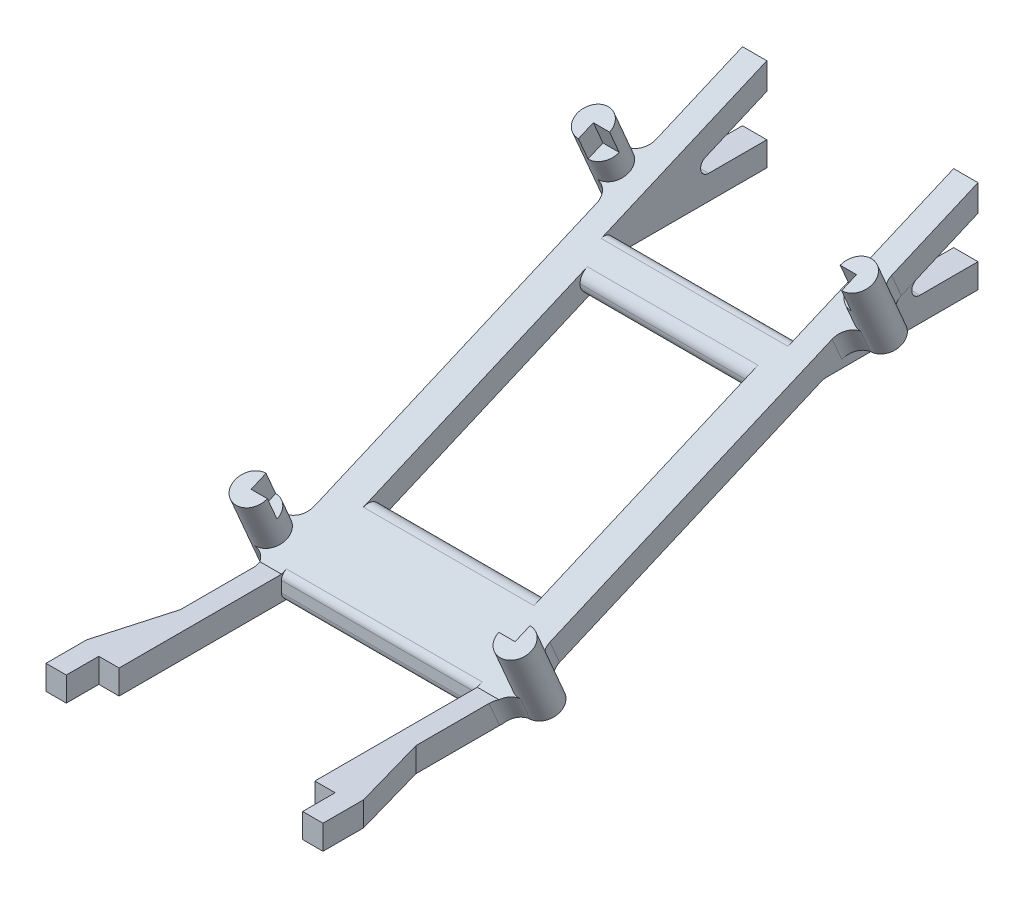
SolidWorks part; units mm, degrees
ref_plane "Front Plane" through (0, 0, 0) normal (0, 0, 1) x (1, 0, 0)
ref_plane "Top Plane" through (0, 0, 0) normal (0, 1, 0) x (1, 0, 0)
ref_plane "Right Plane" through (0, 0, 0) normal (1, 0, 0) x (0, 0, -1)
sketch "Sketch1" plane through (0, 0, 0) normal (1, 0, 0) x (0, 0, -1)
  line L0 (0, 0) -> (0, 30.9996) construction
  line L1 (64.2, 35.525) -> (64.2, -15.505) construction
  line L2 (0, 0) -> (20.617, 0)
  line L3 (20.617, 0) -> (60.2, 17)
  line L4 (60.2, 17) -> (79.2, 17)
  line L5 (79.2, 17) -> (79.2, 20)
  line L6 (79.2, 20) -> (67.1852, 20)
  line L7 (67.1852, 20) -> (79.2, 25.1601)
  line L8 (79.2, 25.1601) -> (79.2, 28.425)
  line L9 (79.2, 28.425) -> (20, 3)
  line L10 (20, 3) -> (0, 3)
  line L11 (0, 3) -> (0, 0)
  dimension "D1" = 64.2
  dimension "D2" = 3
  dimension "D3" = 3
  dimension "D4" = 20
  dimension "D5" = 4
  dimension "D6" = 17
  dimension "D7" = 3
  dimension "D8" = 15
extrude "Boss-Extrude1" add sketch "Sketch1" along normal blind 29
sketch "Sketch2" plane through (0, 3, 0) normal (0, 1, 0) x (1, 0, 0)
  line L0 (29, 0) -> (0, 0) construction
  line L1 (2.45, -20) -> (26.55, -20)
  line L2 (2.45, -20) -> (2.45, 20)
  line L3 (2.45, 20) -> (26.55, 20)
  line L4 (26.55, -20) -> (26.55, 20)
  line L5 (2.45, -20) -> (26.55, 20) construction
  line L6 (2.45, 20) -> (26.55, -20) construction
  line L7 (29, 20) -> (0, 20) construction
  point P0 (14.5, 0)
  dimension "D1" = 24.1
extrude "Cut-Extrude1" cut sketch "Sketch2" against normal blind 28
sketch "Sketch3" plane through (0, 0, 0) normal (0, -1, 0) x (1, 0, 0)
  line L0 (14.5, -60.2) -> (14.5, -10.4345) construction
  line L1 (29, -60.2) -> (0, -60.2) construction
  line L2 (0, -20.617) -> (0, -60.2) construction
  line L3 (4, -55.2) -> (25, -55.2)
  line L4 (4, -55.2) -> (4, -30.617)
  line L5 (4, -30.617) -> (25, -30.617)
  line L6 (25, -55.2) -> (25, -30.617)
  line L7 (4, -55.2) -> (25, -30.617) construction
  line L8 (4, -30.617) -> (25, -55.2) construction
  line L9 (29, -20.617) -> (0, -20.617) construction
  point P4 (14.5, -42.9085)
  dimension "D1" = 4
  dimension "D2" = 10
  dimension "D3" = 5
extrude "Cut-Extrude2" cut sketch "Sketch3" against normal blind 28
sketch "Sketch4" plane through (0, 17, 0) normal (0, -1, 0) x (1, 0, 0)
  line L0 (29, -79.2) -> (0, -79.2) construction
  line L1 (3, -98.2) -> (26, -98.2)
  line L2 (3, -98.2) -> (3, -60.2)
  line L3 (3, -60.2) -> (26, -60.2)
  line L4 (26, -98.2) -> (26, -60.2)
  line L5 (3, -98.2) -> (26, -60.2) construction
  line L6 (3, -60.2) -> (26, -98.2) construction
  line L7 (29, -60.2) -> (0, -60.2) construction
  point P0 (14.5, -79.2)
  point P7 (25.5, -60.2)
  dimension "D1" = 23
extrude "Cut-Extrude3" cut sketch "Sketch4" against normal through all
sketch "Sketch5" plane through (0, 0, 0) normal (0, 1, 0) x (1, 0, 0)
  line L0 (-16.6049, 23) -> (48.1653, 23) construction
  dimension "D1" = 23
sketch "Sketch6" plane through (0, -4.7191, -2.0267) normal (0, 0.9188, 0.3946) x (1, 0, 0)
  line L1 (-16.6049, 21.1334) -> (48.1653, 21.1334) construction
  line L2 (-16.6049, 21.1334) -> (48.1653, 21.1334) construction
  line L3 (48.1653, 22.6334) -> (-16.6049, 22.6334) construction
  line L4 (-1.75, 24.6334) -> (-1.75, 22.6334)
  line L5 (-1.75, 22.6334) -> (0.25, 22.6334)
  line L6 (30.75, 24.6334) -> (30.75, 22.6334)
  line L7 (30.75, 22.6334) -> (28.75, 22.6334)
  line L8 (-1.75, 22.6334) -> (14.5, 31.1154) construction
  line L9 (25, 31.1154) -> (4, 31.1154) construction
  line L10 (14.5, 31.1154) -> (30.75, 22.6334) construction
  circle A0 centre (-1.75, 22.6334) radius 2
  circle A1 centre (30.75, 22.6334) radius 2
  line M14 (0, 83.9896) -> (0, 19.5607)
  line M18 (29, 19.5607) -> (29, 83.9896)
  dimension "D2" = 4
  dimension "D1" = 1.5
  dimension "D3" = 32.5
extrude "Boss-Extrude2" add sketch "Sketch6" along normal blind 6 separate body contours L7 A1 L6 | L4 A0 L5 | A0 L5 M14 | L7 A1 M18
sketch "Sketch7" plane through (0, -4.7191, -2.0267) normal (0, -0.9188, -0.3946) x (1, 0, 0)
  arc A0 (30.75, -24.6334) -> (28.75, -22.6334) centre (30.75, -22.6334) ccw construction
  circle A1 centre (30.75, -22.6334) radius 2
  arc A2 (0.25, -22.6334) -> (-1.75, -24.6334) centre (-1.75, -22.6334) ccw construction
  circle A3 centre (-1.75, -22.6334) radius 2
  point P3 (28.25, -22.9332)
  point P8 (-0.25, -22.9709)
extrude "Boss-Extrude3" add sketch "Sketch7" against normal blind 3
sketch "Sketch8" plane through (0, -4.7191, -2.0267) normal (0, -0.9188, -0.3946) x (1, 0, 0)
  line L0 (-1.75, -20.6334) -> (30.75, -20.6334)
  line L1 (-1.75, -24.6334) -> (30.75, -24.6334)
  circle A0 centre (-1.75, -22.6334) radius 2 construction
  circle A1 centre (-1.75, -22.6334) radius 2
  circle A2 centre (30.75, -22.6334) radius 2 construction
  circle A3 centre (30.75, -22.6334) radius 2
  circle M2 centre (30.75, -22.6334) radius 2
extrude "Boss-Extrude4" add sketch "Sketch8" along normal blind 3 contours A1 L1 L0 M2 | M2 | A1
fillet "Fillet5" radius 1 1 edges at (14.5, 17, -60.2)
fillet "Fillet1" radius 2 6 edges at (1.5, 17, -60.2) (27.5, 17, -60.2) (29, 2.045, -21.5775) (29, 3.6235, -25.2529) (0, 3.6235, -25.2529) (0, 2.045, -21.5775)
sketch "Sketch9" plane through (0, -4.7191, -2.0267) normal (0, 0.9188, 0.3946) x (1, 0, 0)
  line L0 (-1.7, 66.4334) -> (-1.7, 68.4334)
  line L1 (-1.7, 68.4334) -> (0.3, 68.4334)
  line L2 (28.7, 68.4334) -> (30.7, 68.4334)
  line L3 (30.7, 68.4334) -> (30.7, 66.4334)
  line L4 (-1.7, 68.4334) -> (14.5, 57.8698) construction
  line L5 (4, 57.8698) -> (25, 57.8698) construction
  line L6 (14.5, 57.8698) -> (30.7, 68.4334) construction
  line L7 (-1.75, 22.6334) -> (0.25, 22.6334) construction
  line L8 (0.25, 22.6334) -> (28.75, 22.6334) construction
  line L9 (0.3, 68.4334) -> (28.7, 68.4334) construction
  circle A0 centre (-1.7, 68.4334) radius 2
  circle A1 centre (30.7, 68.4334) radius 2
  arc A2 (-1.875, 20.6373) -> (-1.875, 24.6295) centre (-1.75, 22.6334) ccw construction
  arc A3 (30.875, 24.6295) -> (30.875, 20.6373) centre (30.75, 22.6334) ccw construction
  arc A4 (0.25, 22.6334) -> (-1.75, 24.6334) centre (-1.75, 22.6334) ccw construction
  point P20 (28.75, 22.6334)
  point P24 (0.25, 22.6334)
  line M16 (29, 26.6256) -> (29, 83.9896)
  line M22 (0, 83.9896) -> (0, 26.6256)
  dimension "D1" = 32.4
  dimension "D2" = 45.8
extrude "Boss-Extrude5" add sketch "Sketch9" along normal up to surface (6 mm away) separate body contours L1 A0 L0 | L3 A1 L2 | L1 A0 M22 | A1 L2 M16
sketch "Sketch10" plane through (0, -4.7191, -2.0267) normal (0, -0.9188, -0.3946) x (1, 0, 0)
  arc A0 (28.7, -68.4334) -> (30.7, -66.4334) centre (30.7, -68.4334) ccw construction
  circle A1 centre (30.7, -68.4334) radius 2
  arc A2 (-1.7, -66.4334) -> (0.3, -68.4334) centre (-1.7, -68.4334) ccw construction
  circle A3 centre (-1.7, -68.4334) radius 2
  point P6 (0, 0)
  point P8 (30.7348, -66.5062)
extrude "Boss-Extrude6" add sketch "Sketch10" against normal up to surface (3 mm away) up to face at (29.9453, 7.2866, -22.3789)
sketch "Sketch11" plane through (0, -4.7191, -2.0267) normal (0, -0.9188, -0.3946) x (1, 0, 0)
  line L0 (-1.7, -70.4334) -> (30.7, -70.4334)
  line L1 (-1.7, -66.4334) -> (30.7, -66.4334)
  line L2 (3, -62.4009) -> (3, -79.481) construction
  line L3 (26, -79.481) -> (26, -62.4009) construction
  line L4 (3, -62.4009) -> (3, -79.481)
  line L5 (26, -79.481) -> (26, -62.4009)
  circle A0 centre (30.7, -68.4334) radius 2 construction
  circle A1 centre (30.7, -68.4334) radius 2
  circle A2 centre (-1.7, -68.4334) radius 2 construction
  circle A3 centre (-1.7, -68.4334) radius 2
  circle M2 centre (30.7, -68.4334) radius 2
extrude "Boss-Extrude7" add sketch "Sketch11" along normal blind 3 contours A3 L0 L4 L1 | A3 | L5 L0 L1 M2 | M2
fillet "Fillet2" radius 2 4 edges at (0, 20.1187, -63.6606) (0, 21.6972, -67.336) (29, 21.6972, -67.336) (29, 20.1187, -63.6606)
fillet "Fillet3" radius 1 2 edges at (1.5, 20, -67.1852) (27.5, 20, -67.1852)
fillet "Fillet4" radius 1.5 4 edges at (14.5, 7.5597, -30.617) (14.5, 18.1176, -55.2) (14.5, 14.8526, -55.2) (14.5, 4.2948, -30.617)
fillet "Fillet6" radius 1 1 edges at (14.5, 20.265, -60.2)
fillet "Fillet7" radius 1 2 edges at (14.5, 0, -20) (14.5, 3, -20)
sketch "Sketch12" plane through (0, 3, 0) normal (0, 1, 0) x (1, 0, 0)
  line L1 (2.45, 0) -> (0, 0) construction
  line L2 (2.45, 0) -> (0, 0) construction
  line L3 (0, 0) -> (-0.05, 0)
  line L4 (-0.05, 0) -> (-0.05, -4)
  line L5 (-0.05, -4) -> (-2.55, -4)
  line L6 (-2.55, -4) -> (-2.55, 1)
  line L7 (-2.55, 1) -> (0, 10)
  line L8 (0, 18.9993) -> (0, 0) construction
  line L9 (0, 10) -> (0, 0)
  line L10 (2.45, 20) -> (2.45, 0) construction
  line L11 (14.5, 20) -> (14.5, -8.6107) construction
  line L12 (26.55, 20) -> (2.45, 20) construction
  line L13 (26.55, 0) -> (29, 0) construction
  line L14 (29, 10) -> (29, 0)
  line L15 (31.55, 1) -> (29, 10)
  line L16 (31.55, -4) -> (31.55, 1)
  line L17 (29.05, -4) -> (31.55, -4)
  line L18 (29.05, 0) -> (29.05, -4)
  line L19 (29, 0) -> (29.05, 0)
  dimension "D1" = 2.5
  dimension "D2" = 4
  dimension "D3" = 2.5
  dimension "D4" = 10
  dimension "D5" = 5
extrude "Boss-Extrude8" add sketch "Sketch12" against normal up to surface (3 mm away) up to face at (0.9765, 0, -12.3044)
